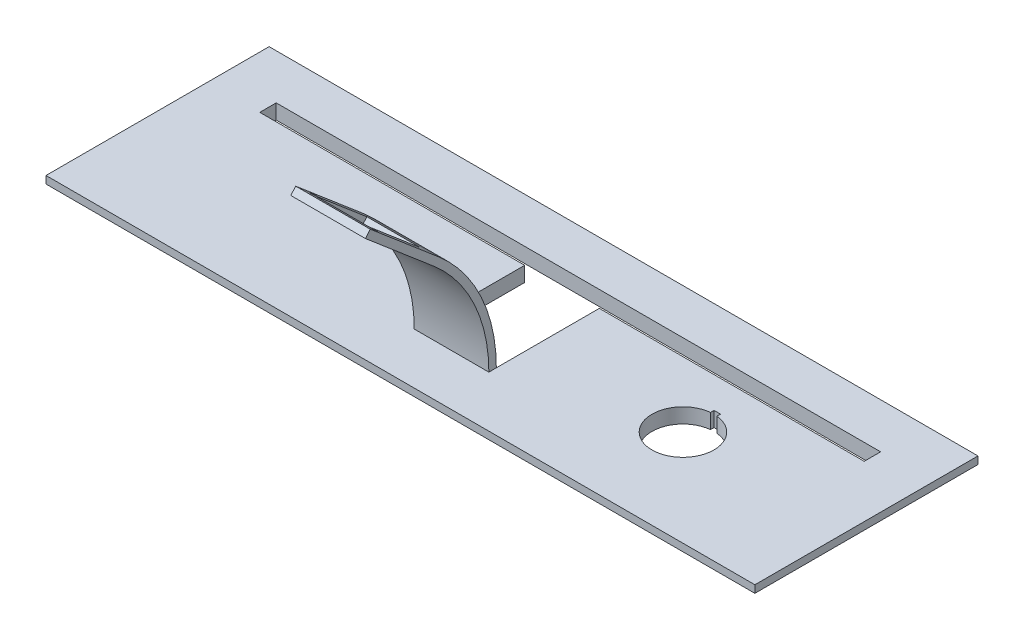
SolidWorks part; units mm, degrees
ref_plane "Front" through (0, 0, 0) normal (0, 0, 1) x (1, 0, 0)
ref_plane "Top" through (0, 0, 0) normal (0, 1, 0) x (1, 0, 0)
ref_plane "Right" through (0, 0, 0) normal (1, 0, 0) x (0, 0, -1)
sketch "Sketch1" plane through (0, 0, 0) normal (0, 1, 0) x (1, 0, 0)
  line L1 (-117.475, 34.798) -> (117.475, 34.798)
  line L2 (-117.475, 34.798) -> (-117.475, -34.798)
  line L3 (-117.475, -34.798) -> (117.475, -34.798)
  line L4 (117.475, 34.798) -> (117.475, -34.798)
  line L5 (-117.475, 34.798) -> (117.475, -34.798) construction
  line L6 (-117.475, -34.798) -> (117.475, 34.798) construction
  point P0 (0, 0)
  dimension "D1" = 69.596
  dimension "D2" = 234.95
extrude "Boss-Extrude1" add sketch "Sketch1" along normal blind 2.54
sketch "Sketch2" plane through (0, 2.54, 0) normal (0, 1, 0) x (1, 0, 0)
  line L8 (120.65, -37.973) -> (120.65, 37.973)
  line L9 (120.65, 37.973) -> (-120.65, 37.973)
  line L10 (-120.65, 37.973) -> (-120.65, -37.973)
  line L11 (-120.65, -37.973) -> (120.65, -37.973)
  line L12 (120.65, -37.973) -> (120.65, 37.973)
  line L13 (120.65, 37.973) -> (-120.65, 37.973)
  line L14 (-120.65, 37.973) -> (-120.65, -37.973)
  line L15 (-120.65, -37.973) -> (120.65, -37.973)
  dimension "D1" = 3.175
extrude "Boss-Extrude2" add sketch "Sketch2" along normal blind 2.54
sketch "Sketch3" plane through (0, 5.08, 0) normal (0, 1, 0) x (1, 0, 0)
  line L1 (-102.87, 22.606) -> (102.87, 22.606)
  line L2 (-102.87, 22.606) -> (-102.87, 12.446)
  line L3 (-102.87, 12.446) -> (102.87, 12.446)
  line L4 (102.87, 22.606) -> (102.87, 12.446)
  line L5 (120.65, 37.973) -> (-120.65, 37.973) construction
  line L6 (-12.7, 17.018) -> (-12.7, 12.446)
  line L7 (-102.87, 17.018) -> (102.87, 17.018)
  line L8 (-102.87, 17.018) -> (-102.87, 22.606)
  line L9 (-102.87, 22.606) -> (102.87, 22.606)
  line L10 (102.87, 17.018) -> (102.87, 22.606)
  line L11 (-12.7, 12.446) -> (12.7, 12.446)
  line L12 (-12.7, 12.446) -> (-12.7, -18.034)
  line L13 (0, -31.2408) -> (0, 31.2408) construction
  line L14 (12.7, 17.018) -> (12.7, 12.446)
  line L15 (-12.7, -18.034) -> (12.7, -18.034)
  line L16 (12.7, 12.446) -> (12.7, -18.034)
  point P0 (0, 0)
  point P8 (0, 0)
  dimension "D1" = 205.74
  dimension "D2" = 10.16
  dimension "D3" = 15.367
  dimension "D4" = 25.4
  dimension "D5" = 4.572
  dimension "D6" = 30.48
extrude "Cut-Extrude2" cut sketch "Sketch3" against normal through all contours L2 L7 L4 L1 | L14 L7 L6 L3 | L16 L3 L12 L15 region at (0, 5.08, -19.812) region at (0, 5.08, -14.732) region at (0, 5.08, 2.794)
sketch "Sketch4" plane through (0, 0, 0) normal (1, 0, 0) x (0, 0, -1)
  line L0 (22.606, 5.08) -> (17.018, 5.08) construction
  line L1 (22.606, 5.08) -> (17.018, 5.08)
  line L2 (-37.7211, 47.6552) -> (-39.3663, 45.72)
  line L4 (-37.973, 2.54) -> (37.973, 2.54)
  line L5 (37.973, 2.54) -> (37.973, 5.08)
  line L6 (37.973, 5.08) -> (-37.973, 5.08)
  line L7 (-37.973, 5.08) -> (-37.973, 2.54)
  line L8 (-37.973, 2.54) -> (37.973, 2.54)
  line L9 (37.973, 2.54) -> (37.973, 5.08)
  line L10 (37.973, 5.08) -> (-37.973, 5.08)
  line L11 (-37.973, 5.08) -> (-37.973, 2.54)
  line L14 (17.018, 5.08) -> (-18.034, 5.08)
  line L15 (-18.034, 5.08) -> (-18.034, 0)
  line L16 (-18.034, 0) -> (17.018, 0)
  line L17 (17.018, 0) -> (17.018, 5.08)
  line L18 (17.018, 5.08) -> (-18.034, 5.08)
  line L20 (-18.034, 0) -> (17.018, 0)
  line L21 (17.018, 0) -> (17.018, 5.08)
  line L23 (-18.034, 5.08) -> (-18.034, 0)
  arc A0 (-18.034, 5.08) -> (-37.7211, 47.6552) centre (-73.914, 5.08) ccw
  arc A1 (-20.574, 5.08) -> (-39.3663, 45.72) centre (-73.914, 5.08) ccw
  dimension "2" = 53.34
  dimension "D5" = 40.64
  dimension "D1" = 0
  dimension "D2" = 0
  dimension "D3" = 2.54
extrude "Boss-Extrude7" add sketch "Sketch4" along normal blind 12.7 and the other way blind 12.7 contours A1 L10 A0 L2 region at (0, 5.5562, 19.304)
sketch "Sketch5" plane through (0, 38.606, 45.4139) normal (0, 0.6477, 0.7619) x (1, 0, 0)
  line L4 (-12.7, 9.3372) -> (12.7, 9.3372)
  line L5 (12.7, 9.3372) -> (12.7, 11.8772)
  line L6 (12.7, 11.8772) -> (-12.7, 11.8772)
  line L7 (-12.7, 11.8772) -> (-12.7, 9.3372)
  line L8 (-12.7, 9.3372) -> (12.7, 9.3372)
  line L9 (12.7, 9.3372) -> (12.7, 11.8772)
  line L10 (12.7, 11.8772) -> (-12.7, 11.8772)
  line L11 (-12.7, 11.8772) -> (-12.7, 9.3372)
  dimension "D1" = 0
extrude "Boss-Extrude8" add sketch "Sketch5" along normal blind 30.48
sketch "Sketch6" plane through (0, 9.0493, -7.6927) normal (0, 0.7619, -0.6477) x (1, 0, 0)
  line L0 (0, -31.2408) -> (0, 31.2408) construction
  line L1 (-9.144, -62.9463) -> (9.144, -62.9463)
  line L2 (-9.144, -62.9463) -> (-9.144, -85.9651)
  line L3 (-9.144, -85.9651) -> (9.144, -85.9651)
  line L4 (12.7, -59.6057) -> (-12.7, -59.6057)
  line L5 (-12.7, -59.6057) -> (-12.7, -90.0857)
  line L6 (-12.7, -90.0857) -> (12.7, -90.0857)
  line L7 (12.7, -90.0857) -> (12.7, -59.6057)
  line L8 (12.7, -59.6057) -> (-12.7, -59.6057)
  line L9 (-12.7, -59.6057) -> (-12.7, -90.0857)
  line L10 (-12.7, -90.0857) -> (12.7, -90.0857)
  line L11 (12.7, -90.0857) -> (12.7, -59.6057)
  line L12 (9.144, -62.9463) -> (9.144, -85.9651)
  line L13 (-9.144, -62.9463) -> (9.144, -85.9651) construction
  line L14 (-9.144, -85.9651) -> (9.144, -62.9463) construction
  point P2 (0, -74.4557)
  dimension "D2" = 18.288
  dimension "D3" = 23.0188
  dimension "D1" = 0
extrude "Cut-Extrude3" cut sketch "Sketch6" against normal up to next contours L12 L1 L2 L3 region at (0, 57.2734, 49.0354)
sketch "Sketch9" plane through (0, 9.0493, -7.6927) normal (0, 0.7619, -0.6477) x (1, 0, 0)
  line L0 (0, -31.2408) -> (0, 31.2408) construction
  line L2 (-9.144, -62.9463) -> (9.144, -62.9463) construction
  circle A0 centre (-10.3187, -85.1713) radius 1
  circle A1 centre (10.3187, -85.1713) radius 1
  dimension "D3" = 2
  dimension "D1" = 22.225
  dimension "D2" = 20.6375
extrude "Cut-Extrude4" cut sketch "Sketch9" against normal up to next
sketch "Sketch10" plane through (0, 5.08, 0) normal (0, 1, 0) x (1, 0, 0)
  line L0 (63.4007, -5.2112) -> (63.4007, 10.0321) construction
  line L1 (62.3007, 6.4723) -> (64.5007, 6.4723)
  line L2 (64.5007, 6.4723) -> (64.5007, 5.2723)
  line L3 (62.3007, 6.4723) -> (62.3007, 5.2723)
  arc A0 (62.3007, 5.2723) -> (64.5007, 5.2723) centre (63.4007, -5.2112) ccw
  point P1 (0, 0)
  point P8 (63.4007, 6.4723)
  dimension "D1" = 21.082
  dimension "D2" = 1.1
  dimension "D3" = 1.2
extrude "Cut-Extrude6" cut sketch "Sketch10" against normal up to next
